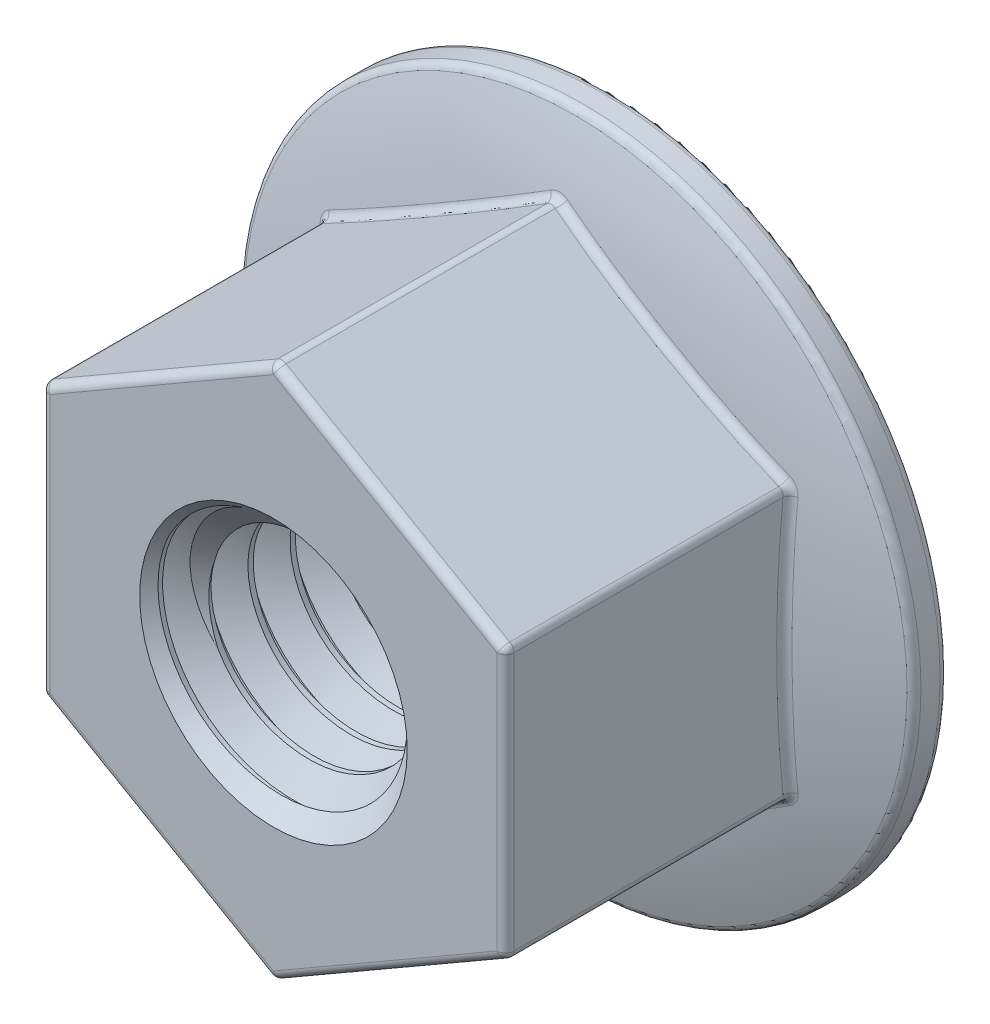
SolidWorks part; units mm, degrees
material "Alloy Steel"
ref_plane "Front Plane" through (0, 0, 0) normal (0, 0, 1) x (1, 0, 0)
ref_plane "Top Plane" through (0, 0, 0) normal (0, 1, 0) x (1, 0, 0)
ref_plane "Right Plane" through (0, 0, 0) normal (1, 0, 0) x (0, 0, -1)
sketch "Sketch1" plane through (0, 0, 0) normal (1, 0, 0) x (0, 0, -1)
  line L0 (0, 0) -> (4, 0) construction
  line L1 (0, 3.1754) -> (-2.75, 1.5877)
  line L2 (-2.75, 1.5877) -> (-2.75, -1.5877)
  line L3 (-2.75, -1.5877) -> (0, -3.1754)
  line L4 (0, -3.1754) -> (2.75, -1.5877)
  line L5 (2.75, -1.5877) -> (2.75, 1.5877)
  line L6 (2.75, 1.5877) -> (0, 3.1754)
  line L7 (3.2, 4) -> (4, 4) construction
  line L8 (-0.4687, 1.5541) -> (-0.2187, 1.1211) construction
  line L9 (-0.2187, 1.1211) -> (0.0313, 1.5541) construction
  line L10 (0.0313, 1.5541) -> (-0.4687, 1.5541) construction
  line L11 (-0.4375, 1.5) -> (0, 1.5) construction
  line L12 (-0.2187, 1.5541) -> (-0.2187, 1.5) construction
  line L13 (-0.2187, 1.5) -> (-0.2187, 1.1752) construction
  line L14 (-0.2187, 1.1752) -> (-0.2187, 1.1211) construction
  line L15 (-0.25, 1.1752) -> (-0.1875, 1.1752)
  line L16 (-0.4531, 1.5271) -> (0.0156, 1.5271)
  line L17 (-0.1875, 1.1752) -> (0.0156, 1.5271)
  line L18 (-0.25, 1.1752) -> (-0.4531, 1.5271)
  circle A0 centre (0, 0) radius 2.75 construction
  point P1 (4, 4)
  point P11 (3.6, 4)
  point P14 (3.2, 4)
  point P15 (0, 1.5)
  point P28 (-0.2187, 1.5271)
  dimension "Height" = 4
  dimension "Flange Diameter" = 8
  dimension "Flange Thickness" = 0.8
  dimension "Thread Size" = 3
  dimension "Pitch" = 0.5
  dimension "D2" = 0.0625
  dimension "Width (Hex)" = 5.5
sketch "Sketch10" plane through (0, 0, 0) normal (0, 0, 1) x (1, 0, 0)
  line L1 (0, 3.1754) -> (-2.75, 1.5877)
  line L2 (-2.75, 1.5877) -> (-2.75, -1.5877)
  line L3 (-2.75, -1.5877) -> (0, -3.1754)
  line L4 (0, -3.1754) -> (2.75, -1.5877)
  line L5 (2.75, -1.5877) -> (2.75, 1.5877)
  line L6 (2.75, 1.5877) -> (0, 3.1754)
  circle A0 centre (0, 0) radius 2.75 construction
  circle A1 centre (0, 0) radius 1.5
extrude "Boss-Extrude1" add sketch "Sketch10" against normal up to vertex (4 mm away) up to point (0, 0, -4)
sketch "Sketch11" plane through (0, 0, 0) normal (1, 0, 0) x (0, 0, -1)
  line L0 (0, 2.75) -> (3.2, 2.75) construction
  line L1 (0, 1.5877) -> (0, 3.1754) construction
  line L2 (3.2, 4) -> (4, 4) construction
  line L3 (3.6, 4) -> (4, 4)
  line L4 (4, 4) -> (4, 1.5)
  line L5 (4, -1.5877) -> (4, 1.5877) construction
  line L6 (4, 1.5) -> (3.2, 1.5)
  line L8 (3.2, 4) -> (3.2, 1.5) construction
  circle A0 centre (0, 0) radius 2.75 construction
  arc A2 (3.6, 4) -> (3.2, 1.5) centre (11.2125, 1.5) ccw
revolve "Revolve2" add sketch "Sketch11" angle 360 about L0
fillet "Fillet1" radius 0.1 20 edges at (-2.75, 1.363, -19.0698) (1.375, -2.3816, 0) (-1.375, -2.3816, 0) (-2.75, 0, 0) (-1.375, 2.3816, 0) (1.375, 2.3816, 0) (2.75, 0, 0) (0, 3.1754, -1.6886) (-2.75, 1.5877, -1.6886) (2.75, -1.5877, -1.6886) (2.75, 1.5877, -1.6886) (-2.75, -1.5877, -1.6886) (0, -3.1754, -1.6886) (4, 0, -4) (4, 0, -3.6)
sketch "Sketch5" plane through (0, 0, 0) normal (0, 0, 1) x (1, 0, 0)
  circle A0 centre (0, 0) radius 1.5 construction
  circle A3 centre (0, 0) radius 1.5
  point P3 (0, -1.5)
curve "Helix/Spiral1" pitch 0.5 height 4.5 turns 9 parameters "pitch"=0.5
sketch "Sketch6" plane through (0, 0, 0) normal (1, 0, 0) x (0, 0, -1)
  line L0 (-0.25, 1.1752) -> (-0.1875, 1.1752) construction
  line L1 (-0.1875, 1.1752) -> (0.0156, 1.5271) construction
  line L2 (-0.4531, 1.5271) -> (0.0156, 1.5271) construction
  line L3 (-0.25, 1.1752) -> (-0.4531, 1.5271) construction
  line L4 (-0.25, 1.1752) -> (-0.1875, 1.1752)
  line L5 (-0.1875, 1.1752) -> (0.0156, 1.5271)
  line L6 (-0.4531, 1.5271) -> (0.0156, 1.5271)
  line L7 (-0.25, 1.1752) -> (-0.4531, 1.5271)
sweep "Sweep1" add profiles "Sketch6" path "Helix/Spiral1"
sketch "Sketch12" plane through (0, 0, 0) normal (1, 0, 0) x (0, 0, -1)
  line L2 (-0.2187, 1.8041) -> (-1.0937, 1.8041)
  line L3 (-1.0937, 1.8041) -> (-1.0937, 0)
  line L5 (0, 0) -> (4, 0) construction
  line L11 (-1.0937, 0) -> (0.4643, 0)
  line L13 (-0.2187, 1.8041) -> (0.4643, 1.1211)
  line L14 (0.4643, 1.1211) -> (0.4643, 0)
  line L15 (2, 0) -> (2, 3.1466) construction
  line L16 (3.2876, 3.1466) -> (0.1, 3.1466) construction
  line L17 (3.5357, 1.1211) -> (3.5357, 0)
  line L18 (4.2187, 1.8041) -> (3.5357, 1.1211)
  line L19 (5.0937, 0) -> (3.5357, 0)
  line L20 (5.0937, 1.8041) -> (5.0937, 0)
  line L21 (4.2187, 1.8041) -> (5.0937, 1.8041)
  dimension "D2" = 0.875
  dimension "D1" = 45
revolve "Cut-Revolve2" cut sketch "Sketch12" angle 360 about L0
equation "\"D3@Helix/Spiral1\"=\"Pitch@Sketch1\"+\"Height@Sketch1\""
equation "\"D2@Sketch1\" = \"Pitch@Sketch1\" / 8"
equation "\"pitch@Helix/Spiral1\" = \"Pitch@Sketch1\""
equation "\"D2@Sketch12\" = \"Pitch@Sketch1\" * 1.75"
